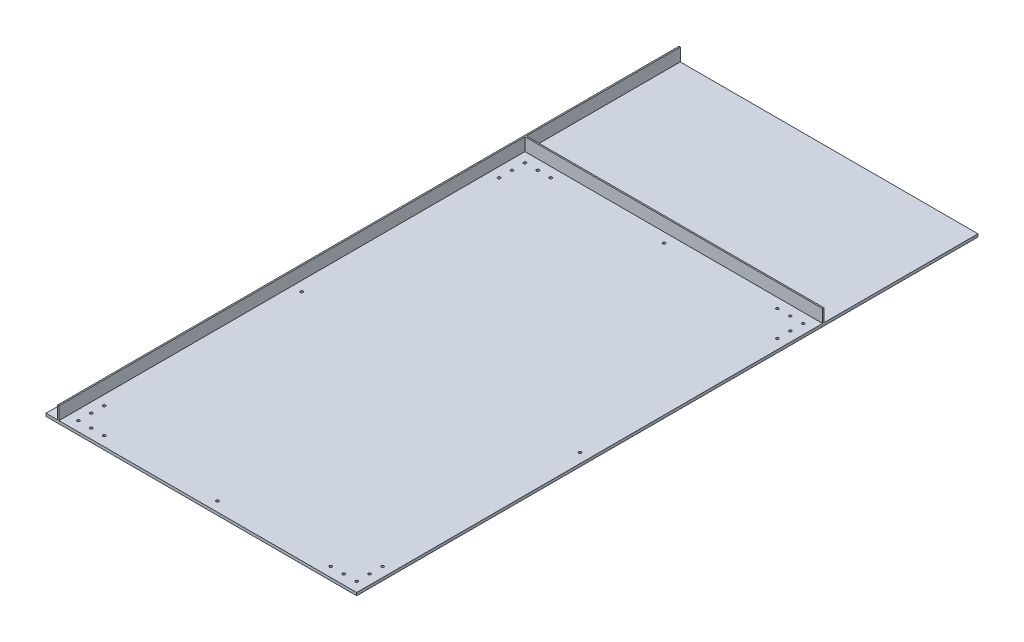
SolidWorks part; units mm, degrees
ref_plane "Front Plane" through (0, 0, 0) normal (0, 0, 1) x (1, 0, 0)
ref_plane "Top Plane" through (0, 0, 0) normal (0, 1, 0) x (1, 0, 0)
ref_plane "Right Plane" through (0, 0, 0) normal (1, 0, 0) x (0, 0, -1)
sketch "Sketch1" plane through (0, 0, 0) normal (0, 1, 0) x (1, 0, 0)
  line L1 (-304.8, 609.6) -> (304.8, 609.6)
  line L2 (-304.8, 609.6) -> (-304.8, -609.6)
  line L3 (-304.8, -609.6) -> (304.8, -609.6)
  line L4 (304.8, 609.6) -> (304.8, -609.6)
  line L5 (-304.8, 609.6) -> (304.8, -609.6) construction
  line L6 (-304.8, -609.6) -> (304.8, 609.6) construction
  point P0 (0, 0)
  dimension "D1" = 609.6
  dimension "D2" = 1219.2
extrude "Boss-Extrude1" add sketch "Sketch1" along normal blind 5.5
sketch "Sketch2" plane through (0, 5.5, 0) normal (0, 1, 0) x (1, 0, 0)
  line L0 (-279.4, 609.6) -> (-279.4, -609.6)
  line L1 (304.8, 609.6) -> (-304.8, 609.6) construction
  line L2 (-304.8, -609.6) -> (304.8, -609.6) construction
  line L3 (304.8, -609.6) -> (304.8, 609.6) construction
  line L4 (-279.4, 307.34) -> (304.8, 307.34)
  dimension "D1" = 1219.2
  dimension "D2" = 584.2
  dimension "D3" = 302.26
extrude "Extrude-Thin1" add sketch "Sketch2" along normal blind 25.4 thin contours L4 thin type one direction wall 2.54
extrude "Extrude-Thin2" add sketch "Sketch2<3>" along normal blind 25.4 thin thin type one direction wall 2.54
sketch "Sketch2<3>" plane through (0, 5.5, 0) normal (0, 1, 0) x (1, 0, 0) same geometry as "Sketch2"
sketch "Sketch3" plane through (0, 5.5, 0) normal (0, 1, 0) x (1, 0, 0)
  line L0 (-279.4, -590.55) -> (304.8, -590.55) construction
  line L1 (-279.4, 304.8) -> (-279.4, -609.6) construction
  line L2 (304.8, -609.6) -> (304.8, 304.8) construction
  line L3 (-279.4, -609.6) -> (304.8, -609.6) construction
  line L4 (-260.35, -609.6) -> (-260.35, 304.8) construction
  line L5 (-279.4, 304.8) -> (304.8, 304.8) construction
  line L6 (-279.4, 304.8) -> (-279.4, -609.6) construction
  line L7 (-279.4, 285.75) -> (304.8, 285.75) construction
  line L8 (285.75, -609.6) -> (285.75, 304.8) construction
  line L9 (-279.4, 304.8) -> (304.8, 304.8) construction
  line L10 (-260.35, -152.4) -> (285.75, -152.4) construction
  line L11 (12.7, 285.75) -> (12.7, -590.55) construction
  point P20 (-260.35, 285.75)
  point P21 (-260.35, 260.35)
  point P22 (-234.95, 285.75)
  point P23 (-260.35, 234.95)
  point P24 (-209.55, 285.75)
  point P29 (285.75, 234.95)
  point P30 (12.7, 285.75)
  point P31 (-260.35, -152.4)
  point P32 (12.7, -590.55)
  point P33 (285.75, -152.4)
  point P34 (285.75, 260.35)
  point P35 (285.75, 285.75)
  point P36 (260.35, 285.75)
  point P37 (234.95, 285.75)
  point P38 (285.75, -539.75)
  point P39 (285.75, -565.15)
  point P40 (285.75, -590.55)
  point P41 (260.35, -590.55)
  point P42 (234.95, -590.55)
  point P43 (-209.55, -590.55)
  point P44 (-234.95, -590.55)
  point P45 (-260.35, -590.55)
  point P46 (-260.35, -565.15)
  point P47 (-260.35, -539.75)
  dimension "D1" = 19.05
  dimension "D2" = 19.05
  dimension "D3" = 19.05
  dimension "D4" = 19.05
  dimension "D5" = 0
  dimension "D6" = 25.4
  dimension "D7" = 25.4
  dimension "D8" = 25.4
  dimension "D9" = 25.4
hole_wizard "Ø5.3 (5.3) Diameter Hole1" positions "Sketch4" profile "Sketch5" hole size "Ø5.3" standard "ANSI Metric" end condition through all
sketch "Sketch4" plane through (0, 5.5, 0) normal (0, 1, 0) x (1, 0, 0)
  point P0 (-260.35, 285.75)
  point P3 (-234.95, 285.75)
  point P6 (-209.55, 285.75)
  point P9 (-260.35, 260.35)
  point P12 (-260.35, 234.95)
  point P15 (12.7, 285.75)
  point P18 (234.95, 285.75)
  point P21 (260.35, 285.75)
  point P24 (285.75, 285.75)
  point P27 (285.75, 260.35)
  point P30 (285.75, 234.95)
  point P33 (-260.35, -152.4)
  point P36 (285.75, -152.4)
  point P39 (-260.35, -539.75)
  point P42 (-260.35, -565.15)
  point P45 (-260.35, -590.55)
  point P48 (-234.95, -590.55)
  point P51 (-209.55, -590.55)
  point P54 (12.7, -590.55)
  point P57 (234.95, -590.55)
  point P60 (260.35, -590.55)
  point P63 (285.75, -590.55)
  point P66 (285.75, -565.15)
  point P69 (285.75, -539.75)
sketch "Sketch5" plane through (-260.35, 5.5, -285.75) normal (1, 0, 0) x (0, 0, 1)
  line L0 (0, 0) -> (0, 5.5)
  line L1 (0, 5.5) -> (2.65, 5.5)
  line L2 (2.65, 5.5) -> (2.65, 0)
  line L5 (2.65, 0) -> (0, 0)
  line L11 (0, -6.35) -> (0, 107.95) construction
  dimension "Thru Hole Dia." = 5.3
  dimension "Thru Hole Depth" = 5.5
